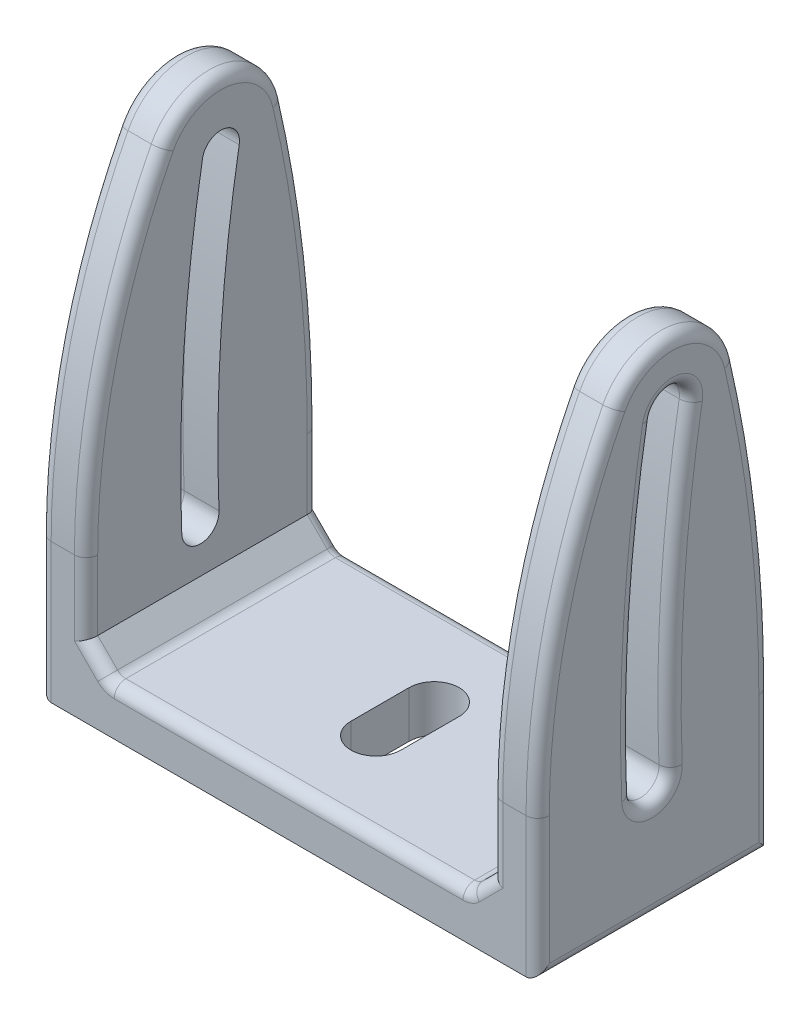
SolidWorks part; units mm, degrees
ref_plane "Front Plane" through (0, 0, 0) normal (0, 0, 1) x (1, 0, 0)
ref_plane "Top Plane" through (0, 0, 0) normal (0, 1, 0) x (1, 0, 0)
ref_plane "Right Plane" through (0, 0, 0) normal (1, 0, 0) x (0, 0, -1)
sketch "Sketch1" plane through (0, 0, 0) normal (1, 0, 0) x (0, 0, -1)
  line L1 (-10, -6) -> (10, -6)
  line L2 (-10, -6) -> (-10, 6)
  line L3 (-10, 6) -> (10, 6) construction
  line L4 (10, -6) -> (10, 6)
  line L5 (-10, -6) -> (10, 6) construction
  line L6 (-10, 6) -> (10, -6) construction
  line L8 (127.716, 9) -> (0, 9) construction
  line L9 (127.716, 9) -> (0, 17.408) construction
  line L10 (0, -6) -> (127.716, -6) construction
  line L11 (127.716, -6) -> (127.716, 9) construction
  line L12 (0, 17.408) -> (0, -6) construction
  line L13 (1.5785, 30.7119) -> (127.716, 9) construction
  line L14 (-0.1792, 4.012) -> (127.716, 9) construction
  arc A0 (-3.4022, 33.2717) -> (7.0344, 31.9742) centre (1.5785, 30.7119) cw
  arc A1 (1.5785, 30.7119) -> (-0.1792, 4.012) centre (127.716, 9) ccw construction
  arc A2 (0.0017, 30.9833) -> (-1.778, 3.9496) centre (127.716, 9) ccw
  arc A3 (3.1553, 30.4405) -> (1.4196, 4.0743) centre (127.716, 9) ccw
  arc A4 (3.1553, 30.4405) -> (0.0017, 30.9833) centre (1.5785, 30.7119) ccw
  arc A5 (-1.778, 3.9496) -> (1.4196, 4.0743) centre (-0.1792, 4.012) ccw
  arc A6 (-10, 6) -> (-3.4022, 33.2717) centre (49.6619, 6) cw
  arc A7 (10, 6) -> (7.0344, 31.9742) centre (-105.23, 6) ccw
  point P0 (0, 0)
  point P13 (0, 17.408)
  dimension "D2" = 8.408
  dimension "D4" = 4
  dimension "D8" = 12
  dimension "D7" = 1.6
  dimension "D1" = 12
  dimension "D3" = 20
  dimension "D5" = 15
  dimension "D6" = 127.716
extrude "Boss-Extrude1" add sketch "Sketch1" along normal blind 42.8
sketch "Sketch2" plane through (0, 0, 10) normal (0, 0, 1) x (1, 0, 0)
  line L0 (42.8, 36.3119) -> (0, 36.3119) construction
  line L1 (4, -2) -> (38.8, -2)
  line L2 (4, -2) -> (4, 36.3119)
  line L3 (4, 36.3119) -> (38.8, 36.3119)
  line L4 (38.8, -2) -> (38.8, 36.3119)
  line L5 (0, 36.3119) -> (4, 36.3119) construction
  line L6 (38.8, 36.3119) -> (42.8, 36.3119) construction
  line L7 (42.8, -6) -> (0, -6) construction
  dimension "D1" = 4
  dimension "D2" = 4
extrude "Cut-Extrude1" cut sketch "Sketch2" against normal through all
chamfer "Chamfer1" distance 2 angle 45 2 edges at (38.8, -2, 0) (4, -2, 0)
fillet "Fillet1" radius 1 38 edges at (38.8, 3, -10) (38.8, 3, 10) (4, 3, -10) (4, 3, 10) (38.8, 36.2691, -2.2694) (4, 36.2691, -2.2694) (5, -1, -10) (5, -1, 10) (37.8, -1, -10) (37.8, -1, 10) (6, -2, 0) (21.4, -2, -10) (36.8, -2, 0) (21.4, -2, 10) (42.8, 36.2691, -2.2694) (0, 36.2691, -2.2694) (38.8, 19.0715, -9.2562) (38.8, 20.0292, 8.3271) (4, 19.0715, -9.2562) (4, 20.0292, 8.3271) (0, 17.3029, -1.5965) (0, 2.4132, 0.1169) (0, 17.5131, 1.5965) (0, 32.2887, -1.8499) (0, 20.0292, 8.3271) (0, 0, 10) (0, -6, 0) (0, 0, -10) (0, 19.0715, -9.2562) (42.8, 2.4132, 0.1169) (42.8, 17.3029, -1.5965) (42.8, 32.2887, -1.8499) (42.8, 17.5131, 1.5965) (42.8, 0, -10) (42.8, -6, 0) (42.8, 0, 10) (42.8, 20.0292, 8.3271) (42.8, 19.0715, -9.2562)
sketch "Sketch3" plane through (0, -2, 0) normal (0, 1, 0) x (1, 0, 0)
  line L0 (21.4, -2.5) -> (21.4, 2.5) construction
  line L3 (19.25, -2.5) -> (19.25, 2.5)
  line L4 (23.55, -2.5) -> (23.55, 2.5)
  line L5 (21.4, 9) -> (21.4, -9) construction
  line L6 (36.3858, 9) -> (6.4142, 9) construction
  line L7 (6.4142, -9) -> (36.3858, -9) construction
  arc A0 (19.25, -2.5) -> (23.55, -2.5) centre (21.4, -2.5) ccw
  arc A1 (23.55, 2.5) -> (19.25, 2.5) centre (21.4, 2.5) ccw
  point P2 (21.4, 0)
  point P15 (21.4, 0)
  dimension "D1" = 4.3
  dimension "D2" = 5
extrude "Cut-Extrude2" cut sketch "Sketch3" against normal through all
